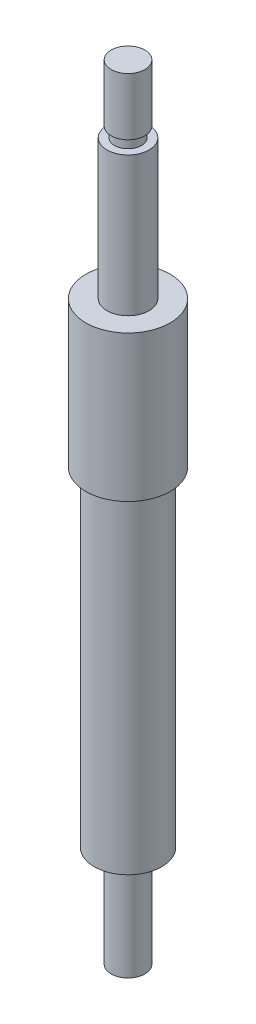
SolidWorks part; units mm, degrees
ref_plane "Front Plane" through (0, 0, 0) normal (0, 0, 1) x (1, 0, 0)
ref_plane "Top Plane" through (0, 0, 0) normal (0, 1, 0) x (1, 0, 0)
ref_plane "Right Plane" through (0, 0, 0) normal (1, 0, 0) x (0, 0, -1)
sketch "Sketch1" plane through (0, 0, 0) normal (0, 0, 1) x (1, 0, 0)
  line L0 (0, 0) -> (0, 67.2246) construction
  line L1 (0, 0) -> (2, 0)
  line L2 (2, 0) -> (2, 12)
  line L3 (2, 12) -> (4, 12)
  line L4 (4, 12) -> (4, 51)
  line L5 (4, 51) -> (5, 51)
  line L7 (5, 68.3) -> (2.5, 68.3)
  line L8 (2.5, 68.3) -> (2.5, 84.8)
  line L9 (2, 92.8) -> (0, 92.8)
  line L10 (2, 92.8) -> (2, 86)
  line L11 (1.6, 84.8) -> (2.5, 84.8)
  line L12 (0, 92.8) -> (0, 0)
  line L13 (5, 68.3) -> (5, 51)
  line L15 (2, 86) -> (1.6, 86)
  line L16 (1.6, 86) -> (1.6, 84.8)
  point P8 (5, 31.8381)
  point P11 (2, 11.5213)
  point P16 (5, 17.7463)
  point P18 (0.9686, 60.9913)
  dimension "D1" = 17.3
  dimension "D2" = 8
  dimension "D3" = 5
  dimension "D4" = 4
  dimension "D5" = 3.2
  dimension "D6" = 16.5
  dimension "D7" = 10
  dimension "D8" = 1.2
  dimension "D9" = 8
  dimension "D10" = 39
  dimension "D11" = 12
revolve "Revolve1" add sketch "Sketch1" angle 360 about L0
